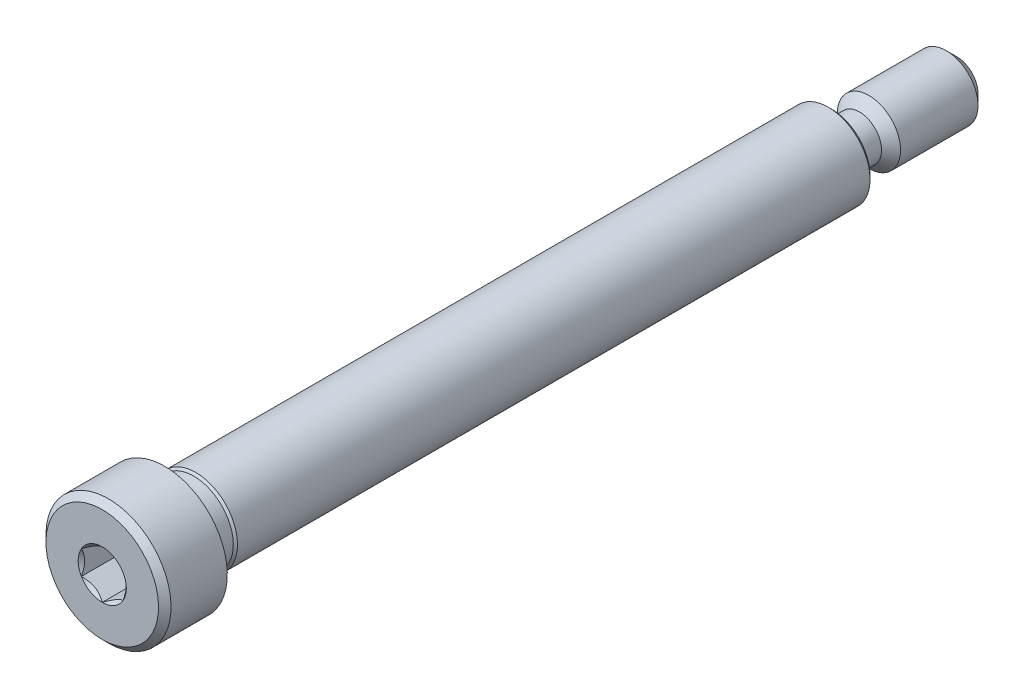
SolidWorks part; units mm, degrees
material "Alloy Steel"
ref_plane "Front Plane" through (0, 0, 0) normal (0, 0, 1) x (1, 0, 0)
ref_plane "Top Plane" through (0, 0, 0) normal (0, 1, 0) x (1, 0, 0)
ref_plane "Right Plane" through (0, 0, 0) normal (1, 0, 0) x (0, 0, -1)
sketch "Sketch2" plane through (0, 0, 0) normal (1, 0, 0) x (0, 0, -1)
  line L0 (-32.5438, 0) -> (32.5438, 0) construction
  line L1 (-32.5438, 0) -> (-32.5438, 4.7625)
  line L2 (-32.5438, 4.7625) -> (-27.7812, 4.7625)
  line L3 (-27.7812, 4.7625) -> (-27.7813, 3.175)
  line L4 (-27.7813, 3.175) -> (23.0188, 3.175)
  line L5 (23.0188, 2.413) -> (32.5438, 2.413)
  line L6 (32.5438, 2.413) -> (32.5438, 0)
  line L7 (32.4776, 2.5276) -> (33.0068, 1.611) construction
  line L8 (33.0068, 1.611) -> (33.5359, 2.5276) construction
  line L9 (33.5359, 2.5276) -> (32.4776, 2.5276) construction
  line L10 (32.5438, 2.413) -> (33.4698, 2.413) construction
  line L11 (33.0068, 2.5276) -> (33.0068, 2.413) construction
  line L12 (33.0068, 2.413) -> (33.0068, 1.7256) construction
  line L13 (33.0068, 1.7256) -> (33.0068, 1.611) construction
  line L14 (32.9406, 1.7256) -> (33.0729, 1.7256)
  line L15 (32.5107, 2.4703) -> (33.5029, 2.4703)
  line L16 (33.0729, 1.7256) -> (33.5029, 2.4703)
  line L17 (32.9406, 1.7256) -> (32.5107, 2.4703)
  line L18 (32.5438, 0) -> (32.5438, -2.413) construction
  line L19 (23.0188, -3.175) -> (23.0188, 0) construction
  line L20 (23.0188, 0) -> (23.0188, 3.175) construction
  line L21 (-32.5438, 0) -> (-32.5438, -4.7625) construction
  point P11 (-25.419, 3.175)
  point P12 (29.8979, -2.413)
  point P22 (33.0068, 2.4703)
  point P23 (22.5425, 0)
  point P25 (-22.5425, 0)
  point P26 (-27.7812, -4.7625)
  point P29 (23.0188, -3.175)
  dimension "Head Height" = 4.7625
  dimension "Shoulder Diameter" = 6.35
  dimension "Screw Size Decimal Equivalent" = 4.826
  dimension "Thread Length" = 9.525
  dimension "Head Diameter" = 9.525
  dimension "Undercut Length" = 2.3622
  dimension "Pitch" = 1.0583
  dimension "D2" = 0.1323
  dimension "D1" = 2.6458
  dimension "D3" = 10.0013
  dimension "D4" = 10.0012
  dimension "Shoulder Length" = 50.8
sketch "Sketch3" plane through (0, 0, 0) normal (0, 0, 1) x (1, 0, 0)
  line L1 (0, 1.8331) -> (-1.5875, 0.9165)
  line L2 (-1.5875, 0.9165) -> (-1.5875, -0.9165)
  line L3 (-1.5875, -0.9165) -> (0, -1.8331)
  line L4 (0, -1.8331) -> (1.5875, -0.9165)
  line L5 (1.5875, -0.9165) -> (1.5875, 0.9165)
  line L6 (1.5875, 0.9165) -> (0, 1.8331)
  circle A0 centre (0, 0) radius 1.5875 construction
  dimension "Drive Size" = 3.175
sketch "Sketch4" plane through (0, 0, 0) normal (1, 0, 0) x (0, 0, -1)
  line L0 (-27.7812, 4.7625) -> (-32.0675, 4.7625)
  line L1 (-32.0675, 4.7625) -> (-32.5438, 4.2862)
  line L2 (-27.7812, 4.7625) -> (-27.7813, 3.175)
  line L3 (-27.7813, 3.175) -> (-27.6225, 3.0162)
  line L4 (-27.6225, 3.0162) -> (-25.5778, 3.0162)
  line L5 (-25.5778, 3.0162) -> (-25.419, 3.175)
  line L6 (-27.7813, 3.175) -> (23.0188, 3.175) construction
  line L7 (-32.5438, 0) -> (32.5438, 0) construction
  line L8 (-25.419, 3.175) -> (22.7647, 3.175)
  line L9 (22.7647, 3.175) -> (23.0188, 2.921)
  line L10 (23.0188, 2.921) -> (23.0188, 0)
  line L11 (23.0188, 3.175) -> (23.0188, 2.921) construction
  line L12 (23.0188, 2.921) -> (23.0188, 2.667) construction
  line L13 (23.0188, 2.667) -> (23.0188, 2.413) construction
  line L14 (-32.5438, 4.2862) -> (-32.5438, 0)
  line L15 (-32.5438, 4.7625) -> (-27.7812, 4.7625) construction
  line L16 (-32.5438, 0) -> (23.0188, 0)
  dimension "D1" = 45
  dimension "D2" = 6.0325
  dimension "D3" = 45
  dimension "D4" = 45
  dimension "D5" = 8.5725
revolve "Revolve1" add sketch "Sketch4" angle 360 about L16
sketch "Sketch5" plane through (0, 0, 32.5438) normal (0, 0, 1) x (1, 0, 0)
  line L0 (1.5875, 0.9165) -> (0, 1.8331) construction
  line L1 (1.5875, -0.9165) -> (1.5875, 0.9165) construction
  line L2 (0, -1.8331) -> (1.5875, -0.9165) construction
  line L3 (-1.5875, -0.9165) -> (0, -1.8331) construction
  line L4 (-1.5875, 0.9165) -> (-1.5875, -0.9165) construction
  line L5 (0, 1.8331) -> (-1.5875, 0.9165) construction
  line L6 (1.5875, 0.9165) -> (0, 1.8331)
  line L7 (1.5875, -0.9165) -> (1.5875, 0.9165)
  line L8 (0, -1.8331) -> (1.5875, -0.9165)
  line L9 (-1.5875, -0.9165) -> (0, -1.8331)
  line L10 (-1.5875, 0.9165) -> (-1.5875, -0.9165)
  line L11 (0, 1.8331) -> (-1.5875, 0.9165)
extrude "Cut-Extrude1" cut sketch "Sketch5" against normal blind 3.5719
sketch "Sketch6" plane through (0, 0, 32.5438) normal (0, 0, 1) x (1, 0, 0)
  circle A0 centre (0, 0) radius 1.8331
extrude "Cut-Extrude4" cut sketch "Sketch6" against normal blind 3.5719 draft 45
sketch "Sketch7" plane through (0, 0, 0) normal (1, 0, 0) x (0, 0, -1)
  line L0 (23.0188, 2.413) -> (31.75, 2.413)
  line L1 (23.0188, 2.413) -> (32.5438, 2.413) construction
  line L2 (31.75, 2.413) -> (32.5438, 1.6192)
  line L3 (32.5438, 2.413) -> (32.5438, 0) construction
  line L4 (32.5438, 1.6192) -> (32.5438, 0)
  line L5 (32.5438, 0) -> (23.0188, 0)
  line L6 (23.0188, -2.921) -> (23.0188, 2.921) construction
  line L7 (23.0188, 0) -> (23.0188, 2.413)
  dimension "D1" = 45
  dimension "D2" = 0.7938
revolve "Revolve2" add sketch "Sketch7" angle 360 about L5
sketch "Sketch10" plane through (0, 0, 0) normal (1, 0, 0) x (0, 0, -1)
  line L0 (23.7427, 1.6891) -> (25.127, 1.6891)
  line L1 (25.127, 1.6891) -> (26.6129, 3.175)
  line L2 (26.6129, 3.175) -> (23.0188, 3.175)
  line L3 (23.0188, 3.175) -> (23.0188, 2.413)
  line L4 (23.0188, -2.921) -> (23.0188, 2.921) construction
  line L5 (32.5438, 0) -> (23.0188, 0) construction
  line L6 (-32.5438, 0) -> (32.5438, 0) construction
  arc A0 (23.0188, 2.413) -> (23.7427, 1.6891) centre (23.7427, 2.413) ccw
  dimension "Flat OD" = 3.3782
  dimension "Flat" = 2.1082
  dimension "D3" = 45
revolve "Cut-Revolve1" cut sketch "Sketch10" angle 360 about L5
sketch "Sketch8" [suppressed] plane through (0, 0, -32.5438) normal (0, 0, -1) x (-1, 0, 0)
  circle A0 centre (0, 0) radius 2.413 construction
  circle A1 centre (0, 0) radius 2.413
curve "Helix/Spiral1" [suppressed] pitch 1.0583 height 10.5833 turns 10
sketch "Sketch9" [suppressed] plane through (0, 0, 0) normal (1, 0, 0) x (0, 0, -1)
  line L0 (32.9406, 1.7256) -> (33.0729, 1.7256) construction
  line L1 (33.0729, 1.7256) -> (33.5029, 2.4703) construction
  line L2 (32.5107, 2.4703) -> (33.5029, 2.4703) construction
  line L3 (32.9406, 1.7256) -> (32.5107, 2.4703) construction
  line L4 (32.9406, 1.7256) -> (33.0729, 1.7256)
  line L5 (33.0729, 1.7256) -> (33.5029, 2.4703)
  line L6 (32.5107, 2.4703) -> (33.5029, 2.4703)
  line L7 (32.9406, 1.7256) -> (32.5107, 2.4703)
ref_plane "Plane1" [suppressed] through (0, 0, -25.127) normal (0, 0, 1) x (1, 0, 0)
split "Split1" [suppressed] bodies to split 138
sweep "Cut-Sweep1" [suppressed] cut profiles "Sketch9" path "Helix/Spiral1"
combine bodies "Combine1" [suppressed] operation type add bodies to combine 141 139
sketch "Sketch11" [suppressed] plane through (0, 0, 32.5438) normal (0, 0, 1) x (1, 0, 0)
  line L0 (-0.0687, 4.7625) -> (0.0687, 4.7625)
  line L1 (0.0687, 4.7625) -> (0, 4.6434)
  line L2 (0, 0) -> (0, 4.7625) construction
  line L3 (0, 4.6434) -> (-0.0687, 4.7625)
  line L4 (0, 0) -> (4.7625, 0) construction
  circle A0 centre (0, 0) radius 4.7625 construction
  point P6 (0, 4.7625)
  dimension "D1" = 9.2869
  dimension "D2" = 60
  dimension "D3" = 0.1375
sketch "Sketch12" [suppressed] plane through (0, 0, 0) normal (1, 0, 0) x (0, 0, -1)
  line L0 (-32.5438, 4.6434) -> (-29.2593, 4.6434)
  line L1 (-28.8528, 5.0499) -> (-28.8528, 4.7625) construction
  line L2 (-32.5438, 4.7625) -> (-27.7812, 4.7625) construction
  arc A0 (-29.2593, 4.6434) -> (-28.8528, 5.0499) centre (-29.2593, 5.0499) ccw
  point P11 (-28.9719, 4.7625)
  dimension "D1" = 1.1906
sweep "Cut-Sweep2" [suppressed] cut profiles "Sketch11" path "Sketch12"
pattern_circular "CirPattern1" [suppressed] count 76 over 360 about axis through (0, 0, 32.5438) along (0, 0, -1) of bodies 143
equation "\"D2@Sketch2\" = \"Pitch@Sketch2\" / 8"
equation "\"D1@Sketch2\"=\"Pitch@Sketch2\"*2.5"
equation "\"D2@Sketch4\"=\"Shoulder Diameter@Sketch2\"*0.95"
equation "\"D5@Sketch4\"=\"Head Diameter@Sketch2\"*0.9"
equation "\"D1@Cut-Extrude1\"=\"Head Height@Sketch2\"*0.75"
equation "\"D1@Cut-Extrude4\"=\"D1@Cut-Extrude1\""
equation "\"D2@Sketch7\"=\"pitch@sketch2\"*0.75"
equation "\"D3@Helix/Spiral1\"=\"Thread Length@Sketch2\"+\"Pitch@Sketch2\""
equation "\"D4@Helix/Spiral1\"=\"Pitch@Sketch2\""
equation "\"D1@Sketch11\"=\"Head Diameter@Sketch2\"*0.975"
equation "\"D1@Sketch12\"=\"Head Height@Sketch2\"*0.25"
equation "\"D1@CirPattern1\"=\"Head Diameter@Sketch2\" * 3.14 / \"D3@Sketch11\" * 0.35"
equation "\"D3@Sketch2\"=\"Thread Length@Sketch2\"*1.05"
equation "\"D4@Sketch2\"=\"D3@Sketch2\""
